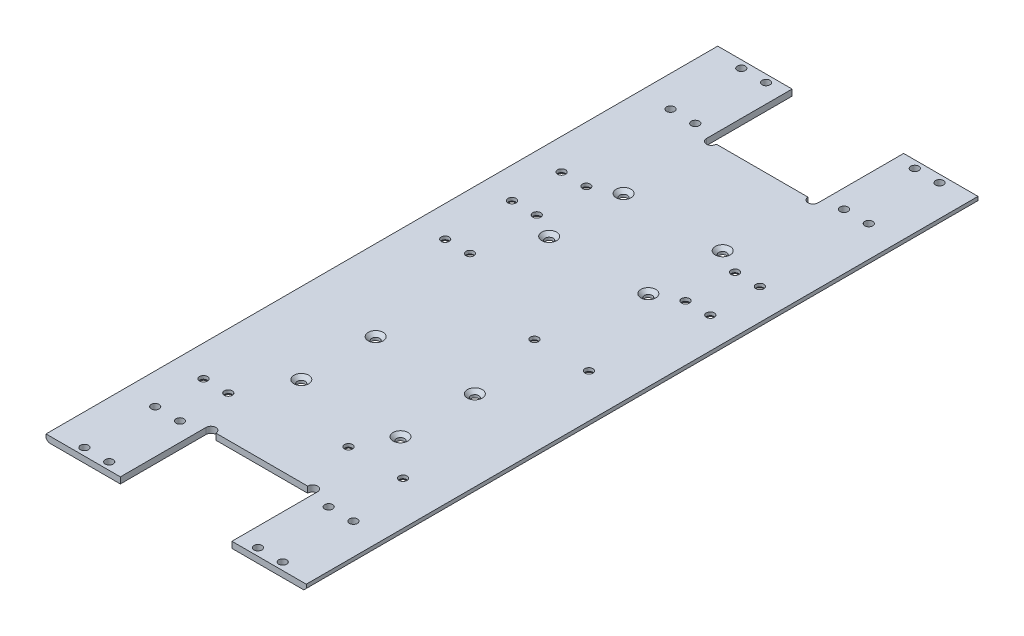
SolidWorks part; units mm, degrees
ref_plane "前视基准面" through (0, 0, 0) normal (0, 0, 1) x (1, 0, 0)
ref_plane "上视基准面" through (0, 0, 0) normal (0, 1, 0) x (1, 0, 0)
ref_plane "右视基准面" through (0, 0, 0) normal (1, 0, 0) x (0, 0, -1)
sketch "草图1" plane through (0, 0, 0) normal (0, 1, 0) x (1, 0, 0)
  line L6 (-52.5, -135.5) -> (52.5, -135.5)
  line L7 (52.5, -135.5) -> (52.5, 135.5)
  line L8 (-52.5, 135.5) -> (52.5, 135.5)
  line L9 (-52.5, -135.5) -> (-52.5, 135.5)
  point P8 (-50, 0)
extrude "凸台-拉伸1" add sketch "草图1" along normal blind 2.5
sketch "草图2" plane through (0, 2.5, 0) normal (0, 1, 0) x (1, 0, 0)
  circle A14 centre (35, -3.95) radius 1.6
  circle A15 centre (13, -3.95) radius 1.6
  circle A18 centre (35, -78.95) radius 1.6
  circle A19 centre (13, -78.95) radius 1.6
  circle A32 centre (20, -35) radius 1.6
  circle A33 centre (-20, -35) radius 1.6
  circle A34 centre (20, -65) radius 1.6
  circle A35 centre (-20, -65) radius 1.6
  circle A36 centre (-20, 35) radius 1.6
  circle A37 centre (20, 35) radius 1.6
  circle A40 centre (-20, 65) radius 1.6
  circle A41 centre (20, 65) radius 1.6
extrude "切除-拉伸1" cut sketch "草图2" against normal blind 10
sketch "草图7" plane through (0, 2.5, 0) normal (0, 1, 0) x (1, 0, 0)
  line L0 (0, -1.375) -> (0, 1.375) construction
  circle A0 centre (-40, 60) radius 1.6
  circle A1 centre (-30, 60) radius 1.6
  circle A2 centre (30, 60) radius 1.6
  circle A3 centre (40, 60) radius 1.6
  circle A4 centre (-40, 40) radius 1.6
  circle A5 centre (-30, 40) radius 1.6
  circle A6 centre (30, 40) radius 1.6
  circle A7 centre (40, 40) radius 1.6
  dimension "D1" = 2
chamfer "倒角4" distance 1.4 angle 45 8 edges at (-20, 2.5, 63.4) (-20, 2.5, 33.4) (20, 2.5, 66.6) (20, 2.5, 36.6) (-20, 2.5, -33.4) (-20, 2.5, -63.4) (20, 2.5, -36.6) (20, 2.5, -66.6)
chamfer "倒角5" distance 1 angle 45 2 edges at (52.5, 0, 0) (-52.5, 0, 0)
sketch "草图4" plane through (0, 0, 0) normal (0, -1, 0) x (1, 0, 0)
  line L0 (1.375, 0) -> (-1.375, 0) construction
  line L1 (-51.5, 135.5) -> (51.5, 135.5) construction
  line L2 (0, 100.95) -> (22.5, 100.95)
  line L3 (22.5, 100.95) -> (22.5, 135.5)
  line L4 (22.5, 135.5) -> (-22.5, 135.5)
  line L5 (-22.5, 135.5) -> (-22.5, 100.95)
  line L6 (-22.5, 100.95) -> (0, 100.95)
  line L7 (-22.5, -100.95) -> (0, -100.95)
  line L8 (-22.5, -135.5) -> (-22.5, -100.95)
  line L9 (22.5, -135.5) -> (-22.5, -135.5)
  line L10 (22.5, -100.95) -> (22.5, -135.5)
  line L11 (0, -100.95) -> (22.5, -100.95)
extrude "切除-拉伸2" cut sketch "草图4" against normal blind 10
sketch "草图6" plane through (0, 0, 0) normal (0, -1, 0) x (1, 0, 0)
  line L0 (0, -1.375) -> (0, 1.375) construction
  line L2 (1.375, 0) -> (-1.375, 0) construction
  circle A0 centre (-40, 132.5) radius 1.6
  circle A1 centre (-30, 132.5) radius 1.6
  circle A2 centre (-30, 103.95) radius 1.6
  circle A3 centre (-40, 103.95) radius 1.6
  circle A4 centre (40, 103.95) radius 1.6
  circle A5 centre (30, 103.95) radius 1.6
  circle A6 centre (30, 132.5) radius 1.6
  circle A7 centre (40, 132.5) radius 1.6
  circle A8 centre (40, -132.5) radius 1.6
  circle A9 centre (30, -132.5) radius 1.6
  circle A10 centre (30, -103.95) radius 1.6
  circle A11 centre (40, -103.95) radius 1.6
  circle A12 centre (-40, -103.95) radius 1.6
  circle A13 centre (-30, -103.95) radius 1.6
  circle A14 centre (-30, -132.5) radius 1.6
  circle A15 centre (-40, -132.5) radius 1.6
extrude "切除-拉伸3" cut sketch "草图6" against normal blind 10
extrude "切除-拉伸4" cut sketch "草图7" against normal blind 10
sketch "草图8" plane through (0, 0, 0) normal (0, -1, 0) x (1, 0, 0)
  line L4 (-40, 132.5) -> (-30, 132.5)
  circle A1 centre (-40, 84.45) radius 1.6
  circle A2 centre (-30, 84.45) radius 1.6
  circle A3 centre (-40, -13.05) radius 1.6
  circle A4 centre (-30, -13.05) radius 1.6
extrude "切除-拉伸5" cut sketch "草图8" against normal blind 10 contours A1 | A2 | A4 | A3 region at (-40, 0, 84.45)
sketch "草图9" plane through (0, 0, 0) normal (0, -1, 0) x (1, 0, 0)
  line L0 (0, -1.375) -> (0, 1.375) construction
  line L1 (1.375, 0) -> (-1.375, 0) construction
  line L2 (-22.5, 100.95) -> (22.5, 100.95) construction
  circle A3 centre (20.5, 100.95) radius 2
  circle A4 centre (-20.5, 100.95) radius 2
  circle A5 centre (-20.5, -100.95) radius 2
  circle A6 centre (20.5, -100.95) radius 2
extrude "切除-拉伸6" cut sketch "草图9" against normal blind 10
chamfer "倒角3" distance 1.2 angle 45 16 edges at (13, 0, 2.35) (35, 0, 2.35) (35, 0, 77.35) (13, 0, 77.35) (40, 0, -61.6) (30, 0, -61.6) (-30, 0, -61.6) (-40, 0, -61.6) (-30, 0, -14.65) (-40, 0, -14.65) (-30, 0, 82.85) (-40, 0, 82.85) (-40, 0, -41.6) (-30, 0, -41.6) (30, 0, -41.6) (40, 0, -41.6)
